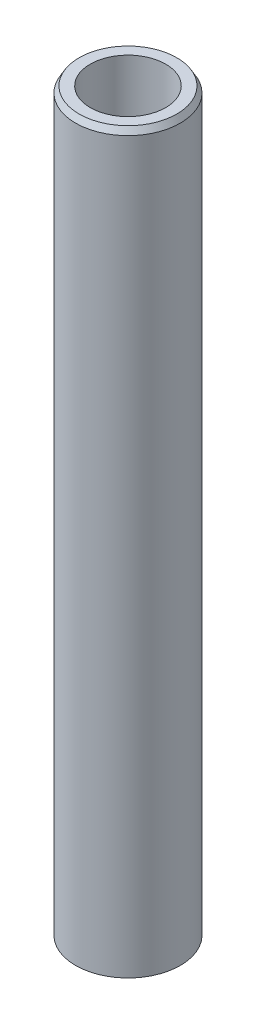
SolidWorks part; units mm, degrees
ref_plane "Front Plane" through (0, 0, 0) normal (0, 0, 1) x (1, 0, 0)
ref_plane "Top Plane" through (0, 0, 0) normal (0, 1, 0) x (1, 0, 0)
ref_plane "Right Plane" through (0, 0, 0) normal (1, 0, 0) x (0, 0, -1)
sketch "Sketch1" plane through (0, 0, 0) normal (0, 1, 0) x (1, 0, 0)
  circle A0 centre (0, 0) radius 42.5
  dimension "SHAFT_OD" = 85
extrude "Boss-Extrude1" add sketch "Sketch1" along normal blind 600
sketch "Sketch2" plane through (0, 0, 0) normal (0, 1, 0) x (1, 0, 0)
  circle A0 centre (0, 0) radius 30.6057
  dimension "BORE_D" = 61.2114
extrude "Cut-Extrude1" cut sketch "Sketch2" along normal through all
chamfer "Chamfer1" distance 4.9619 angle 30 2 edges at (0, 600, 42.5) (0, 0, 42.5) first distance on face at (0, 600, 42.5) first distance on face at (0, 0, 30.6057)
